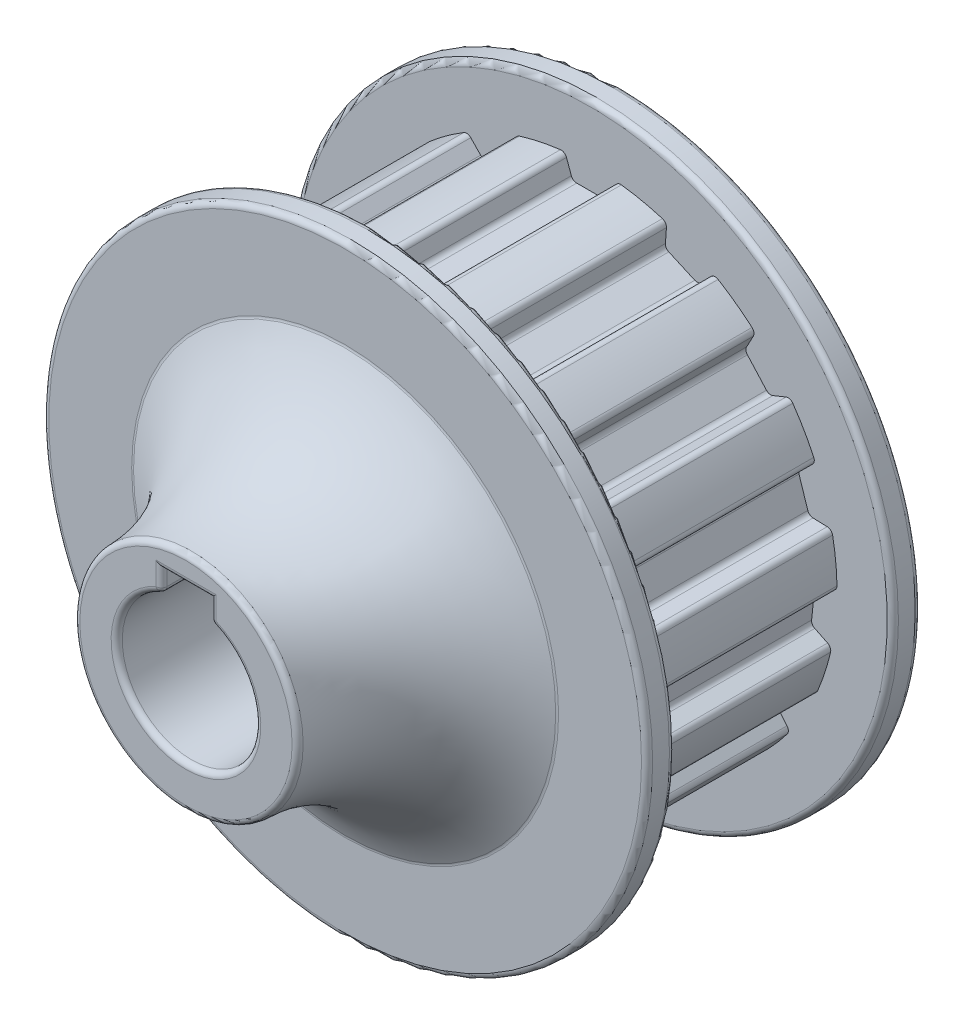
SolidWorks part; units mm, degrees
ref_plane "Front Plane" through (0, 0, 0) normal (0, 0, 1) x (1, 0, 0)
ref_plane "Top Plane" through (0, 0, 0) normal (0, 1, 0) x (1, 0, 0)
ref_plane "Right Plane" through (0, 0, 0) normal (1, 0, 0) x (0, 0, -1)
sketch "Sketch1" plane through (0, 0, 0) normal (0, 1, 0) x (1, 0, 0)
  line L0 (0, 36.1296) -> (0, -19.4741) construction
sketch "Sketch7" plane through (0, 0, 0) normal (0, 0, 1) x (1, 0, 0)
  line L0 (0, 0) -> (0, 20.9536) construction
  line L1 (-2.325, 21.9086) -> (-2.9401, 23.5986) construction
  line L2 (-2.325, 21.9086) -> (-1.6298, 19.9986) construction
  line L3 (-1.6298, 19.9986) -> (1.6298, 19.9986) construction
  line L4 (1.6298, 19.9986) -> (2.325, 21.9086) construction
  line L5 (2.325, 21.9086) -> (-2.325, 21.9086) construction
  line L6 (0, 19.9986) -> (0, 21.9086) construction
  line L7 (2.325, 21.9086) -> (2.9401, 23.5986) construction
  line L8 (-2.9401, 23.5986) -> (2.9401, 23.5986) construction
  line L9 (0, 0) -> (8.5226, 19.1421) construction
  line L10 (8.5226, 19.1421) -> (8.9611, 20.1269) construction
  line L11 (0, 21.9086) -> (0, 22.0316) construction
  line L12 (0, 22.0316) -> (0, 23.7811) construction
  line L13 (0, 22.9064) -> (9.3169, 20.926) construction
  line L14 (8.9611, 20.1269) -> (9.6726, 21.7251) construction
  circle A1 centre (0, 0) radius 20.9536 construction
  circle A2 centre (-1.2727, 20.5086) radius 0.51 construction
  circle A3 centre (1.2727, 20.5086) radius 0.51 construction
  circle A4 centre (0, 0) radius 22.0316
  circle A5 centre (0, 0) radius 23.7811 construction
  dimension "D3" = 40
  dimension "D6" = 1.02
  dimension "D1" = 3.6
  dimension "D2" = 24
  dimension "D7" = 9.525
  dimension "D4" = 1.91
  dimension "D5" = 4.65
extrude "Boss-Extrude1" add sketch "Sketch7" along normal blind 7.25 and the other way blind 7.25 contours A4 region at (0, 0, 0)
sketch "Sketch14" plane through (0, 0, 0) normal (1, 0, 0) x (0, 0, -1)
  line L0 (-21.5, 0) -> (-21.5, 10)
  line L1 (-21.5, 0) -> (0, 0)
  line L2 (0, 0) -> (0, 19)
  line L3 (0, 19) -> (-7.25, 19)
  line L4 (-7.25, 19) -> (-21.5, 10)
  line L5 (-7.25, 22.0316) -> (-7.25, -22.0316) construction
  line L6 (-21.5, 7.0431) -> (-2.5683, 19) construction
  arc A0 (-7.25, 19) -> (-21.5, 10) centre (-21.2919, 25.4517) cw
  dimension "D1" = 10
  dimension "D2" = 19
  dimension "D3" = 21.5
  dimension "D4" = 2.5
revolve "Revolve1" add sketch "Sketch14" angle 360 about L0 region at (0, 7.3866, 9.0486) region at (0, 9.3218, 19.3148) region at (0, 17.2024, 6.8722)
sketch "Sketch9" plane through (0, 0, 0) normal (0, 0, 1) x (1, 0, 0)
  line L0 (2, 0) -> (-2, 0) construction
  line L1 (-2, 0) -> (-2, 7.5) construction
  line L2 (-2, 7.5) -> (2, 7.5) construction
  line L3 (2, 7.5) -> (2, 0) construction
  circle A0 centre (0, 0) radius 6 construction
  dimension "D1" = 12
  dimension "D2" = 4
  dimension "D3" = 7.5
sketch "Sketch10" plane through (0, 0, 0) normal (0, 0, 1) x (1, 0, 0)
  line L0 (2, 0) -> (-2, 0) construction
  line L1 (-2.2, 7.7) -> (2.2, 7.7)
  line L2 (-2.2, 7.7) -> (-2.2, 0)
  line L3 (-2.2, 0) -> (2.2, 0)
  line L4 (2.2, 7.7) -> (2.2, 0)
  line L5 (-2, 7.5) -> (2, 7.5) construction
  line L6 (2, 7.5) -> (2, 0) construction
  circle A0 centre (0, 0) radius 6.2
  circle A1 centre (0, 0) radius 6 construction
  dimension "D1" = 0.2
  dimension "D2" = 0.2
  dimension "D3" = 0.2
extrude "Cut-Extrude3" cut sketch "Sketch10" against normal through all both and the other way through all contours A0 L4 L1 L2 | L2 A0 L4 L3 | L4 A0 L2 L3 region at (0, 6.8793, 0) region at (0, 3.0348, 0) region at (0, -0.8613, 0)
sketch "Sketch11" plane through (0, 0, 0) normal (0, 1, 0) x (1, 0, 0)
  line L0 (22.0316, 7.25) -> (-22.0316, 7.25) construction
  line L1 (11, 7.25) -> (17.5, 7.25)
  line L2 (11, 7.25) -> (11, 4.75)
  line L3 (11, 4.75) -> (17.5, 4.75)
  line L4 (17.5, 7.25) -> (17.5, 4.75)
  line L5 (-22.0316, -7.25) -> (22.0316, -7.25) construction
  line L6 (11, -7.25) -> (17.5, -7.25)
  line L7 (11, -7.25) -> (11, -4.75)
  line L8 (11, -4.75) -> (17.5, -4.75)
  line L9 (17.5, -7.25) -> (17.5, -4.75)
  line L11 (11, 4.75) -> (11, -4.75) construction
  line L12 (17.5, -4.75) -> (17.5, 4.75) construction
  line L13 (6.2, 7.25) -> (-6.2, 7.25) construction
  line L14 (0, 7.25) -> (22.5, 7.25)
  line L15 (0, 7.25) -> (0, -7.25)
  line L16 (0, -7.25) -> (22.5, -7.25)
  line L17 (22.5, 7.25) -> (22.5, -7.25)
  line L18 (-6.2, -7.25) -> (6.2, -7.25) construction
  line L19 (6, 7.25) -> (6, -7.25) construction
  dimension "D1" = 22.5
  dimension "D2" = 6
  dimension "D3" = 5
  dimension "D4" = 5
  dimension "D5" = 2.5
revolve "Cut-Revolve1" [suppressed] cut sketch "Sketch11" angle 360 about L0
sketch "Sketch15" plane through (0, 0, -7.25) normal (0, 0, -1) x (-1, 0, 0)
  circle A0 centre (0, 0) radius 8.0081
  circle A1 centre (0, 0) radius 2.25
  dimension "D1" = 4.5
extrude "Boss-Extrude2" add sketch "Sketch15" against normal blind 5.5
sketch "Sketch16" plane through (0, 0, -7.25) normal (0, 0, -1) x (-1, 0, 0)
  circle A0 centre (0, 0) radius 5
  dimension "D1" = 10
extrude "Cut-Extrude4" cut sketch "Sketch16" against normal blind 3
sketch "Sketch17" plane through (0, 0, -7.25) normal (0, 0, -1) x (-1, 0, 0)
  circle A0 centre (0, 0) radius 22.0316
  circle A1 centre (0, 0) radius 22.0316 construction
  circle A2 centre (0, 0) radius 5
  circle A3 centre (0, 0) radius 5 construction
extrude "Boss-Extrude3" add sketch "Sketch17" along normal blind 7.5
sketch "Sketch8" plane through (0, 0, 0) normal (0, 0, 1) x (1, 0, 0)
  line L6 (-1.6298, 19.9986) -> (-2.3698, 22.0316)
  line L7 (-2.3698, 22.0316) -> (2.3698, 22.0316)
  line L8 (2.3698, 22.0316) -> (1.6298, 19.9986)
  line L9 (1.6298, 19.9986) -> (-1.6298, 19.9986)
  line L10 (-2.325, 21.9086) -> (-1.6298, 19.9986) construction
  line L11 (1.6298, 19.9986) -> (2.325, 21.9086) construction
  line L12 (6.6453, 18.9326) -> (6.7962, 21.0908)
  line L13 (6.7962, 21.0908) -> (11.126, 19.163)
  line L14 (11.126, 19.163) -> (9.6231, 17.6067)
  line L15 (9.6231, 17.6067) -> (6.6453, 18.9326)
  line L16 (13.7713, 14.5929) -> (14.787, 16.5031)
  line L17 (14.787, 16.5031) -> (17.9584, 12.981)
  line L18 (17.9584, 12.981) -> (15.9524, 12.1705)
  line L19 (15.9524, 12.1705) -> (13.7713, 14.5929)
  line L20 (18.5162, 7.73) -> (20.221, 9.0619)
  line L21 (20.221, 9.0619) -> (21.6856, 4.5544)
  line L22 (21.6856, 4.5544) -> (19.5235, 4.6299)
  line L23 (19.5235, 4.6299) -> (18.5162, 7.73)
  line L24 (20.0594, -0.4695) -> (22.1587, 0.0539)
  line L25 (22.1587, 0.0539) -> (21.6632, -4.6597)
  line L26 (21.6632, -4.6597) -> (19.7187, -3.7113)
  line L27 (19.7187, -3.7113) -> (20.0594, -0.4695)
  line L28 (18.1342, -8.5879) -> (20.2649, -8.9635)
  line L29 (20.2649, -8.9635) -> (17.8951, -13.0681)
  line L30 (17.8951, -13.0681) -> (16.5044, -11.4108)
  line L31 (16.5044, -11.4108) -> (18.1342, -8.5879)
  line L32 (13.0734, -15.2212) -> (14.8671, -16.4311)
  line L33 (14.8671, -16.4311) -> (11.0327, -19.2169)
  line L34 (11.0327, -19.2169) -> (10.4363, -17.1372)
  line L35 (10.4363, -17.1372) -> (13.0734, -15.2212)
  line L36 (5.7521, -19.2227) -> (6.8986, -21.0575)
  line L37 (6.8986, -21.0575) -> (2.2626, -22.0429)
  line L38 (2.2626, -22.0429) -> (2.5637, -19.9005)
  line L39 (2.5637, -19.9005) -> (5.7521, -19.2227)
  line L40 (-2.5637, -19.9005) -> (-2.2626, -22.0429)
  line L41 (-2.2626, -22.0429) -> (-6.8986, -21.0575)
  line L42 (-6.8986, -21.0575) -> (-5.7521, -19.2227)
  line L43 (-5.7521, -19.2227) -> (-2.5637, -19.9005)
  line L44 (-10.4363, -17.1372) -> (-11.0327, -19.2169)
  line L45 (-11.0327, -19.2169) -> (-14.8671, -16.4311)
  line L46 (-14.8671, -16.4311) -> (-13.0734, -15.2212)
  line L47 (-13.0734, -15.2212) -> (-10.4363, -17.1372)
  line L48 (-16.5044, -11.4108) -> (-17.8951, -13.0681)
  line L49 (-17.8951, -13.0681) -> (-20.2649, -8.9635)
  line L50 (-20.2649, -8.9635) -> (-18.1342, -8.5879)
  line L51 (-18.1342, -8.5879) -> (-16.5044, -11.4108)
  line L52 (-19.7187, -3.7113) -> (-21.6632, -4.6597)
  line L53 (-21.6632, -4.6597) -> (-22.1587, 0.0539)
  line L54 (-22.1587, 0.0539) -> (-20.0594, -0.4695)
  line L55 (-20.0594, -0.4695) -> (-19.7187, -3.7113)
  line L56 (-19.5235, 4.6299) -> (-21.6856, 4.5544)
  line L57 (-21.6856, 4.5544) -> (-20.221, 9.0619)
  line L58 (-20.221, 9.0619) -> (-18.5162, 7.73)
  line L59 (-18.5162, 7.73) -> (-19.5235, 4.6299)
  line L60 (-15.9524, 12.1705) -> (-17.9584, 12.981)
  line L61 (-17.9584, 12.981) -> (-14.787, 16.5031)
  line L62 (-14.787, 16.5031) -> (-13.7713, 14.5929)
  line L63 (-13.7713, 14.5929) -> (-15.9524, 12.1705)
  line L64 (-9.6231, 17.6067) -> (-11.126, 19.163)
  line L65 (-11.126, 19.163) -> (-6.7962, 21.0908)
  line L66 (-6.7962, 21.0908) -> (-6.6453, 18.9326)
  line L67 (-6.6453, 18.9326) -> (-9.6231, 17.6067)
  circle A0 centre (0, 0) radius 22.0316 construction
  point P119 (0, 0)
  dimension "D1" = 15
extrude "Cut-Extrude2" cut sketch "Sketch8" against normal through all both and the other way through all
fillet "Fillet2" radius 0.51 60 edges at (-6.787, 20.9602, -3.75) (-11.035, 19.0689, -3.75) (-14.7256, 16.3875, -3.75) (-17.837, 12.9319, -3.75) (-20.1179, 8.9813, -3.75) (-21.5548, 4.5589, -3.75) (-22.0316, 0.0222, -3.75) (-21.5456, -4.6023, -3.75) (-20.1359, -8.9408, -3.75) (-17.8109, -12.9678, -3.75) (-14.7585, -16.3578, -3.75) (-10.9966, -19.0911, -3.75) (-6.8293, -20.9465, -3.75) (-2.2809, -21.9133, -3.75) (2.2809, -21.9133, -3.75) (6.8293, -20.9465, -3.75) (10.9966, -19.0911, -3.75) (14.7585, -16.3578, -3.75) (17.8109, -12.9678, -3.75) (20.1359, -8.9408, -3.75) (21.5456, -4.6023, -3.75) (22.0316, 0.0222, -3.75) (21.5548, 4.5589, -3.75) (20.1179, 8.9813, -3.75) (17.837, 12.9319, -3.75) (14.7256, 16.3875, -3.75) (11.035, 19.0689, -3.75) (6.787, 20.9602, -3.75) (2.325, 21.9086, -3.75) (-6.6453, 18.9326, -3.75) (-9.6231, 17.6067, -3.75) (-13.7713, 14.5929, -3.75) (-15.9524, 12.1705, -3.75) (-18.5162, 7.73, -3.75) (-19.5235, 4.6299, -3.75) (-20.0594, -0.4695, -3.75) (-19.7187, -3.7113, -3.75) (-18.1342, -8.5879, -3.75) (-16.5044, -11.4108, -3.75) (-13.0734, -15.2212, -3.75) (-10.4363, -17.1372, -3.75) (-5.7521, -19.2227, -3.75) (-2.5637, -19.9005, -3.75) (2.5637, -19.9005, -3.75) (5.7521, -19.2227, -3.75) (10.4363, -17.1372, -3.75) (13.0734, -15.2212, -3.75) (16.5044, -11.4108, -3.75) (18.1342, -8.5879, -3.75) (19.7187, -3.7113, -3.75) (20.0594, -0.4695, -3.75) (19.5235, 4.6299, -3.75) (18.5162, 7.73, -3.75) (15.9524, 12.1705, -3.75) (13.7713, 14.5929, -3.75) (9.6231, 17.6067, -3.75) (6.6453, 18.9326, -3.75) (1.6298, 19.9986, -3.75) (-1.6298, 19.9986, -3.75) (-2.325, 21.9086, -3.75)
sketch "Sketch18" plane through (0, 0, -14.75) normal (0, 0, -1) x (-1, 0, 0)
  circle A0 centre (0, 0) radius 5
  circle A1 centre (0, 0) radius 27.0316
  circle A2 centre (0, 0) radius 22.0316
  circle A3 centre (0, 0) radius 5 construction
  arc A4 (-2.7297, 21.8619) -> (-6.3983, 21.0821) centre (0, 0) ccw construction
  dimension "D1" = 5
extrude "Boss-Extrude4" add sketch "Sketch18" along normal blind 2.5 contours A1 A2 | A2 A0 region at (26.2671, 0, -14.75) region at (21.4085, 0, -14.75)
sketch "Sketch19" plane through (0, 0, 7.25) normal (0, 0, 1) x (1, 0, 0)
  circle A0 centre (0, 0) radius 19
  circle A1 centre (0, 0) radius 27.0316
  circle A2 centre (0, 0) radius 27.0316 construction
  circle A3 centre (0, 0) radius 19 construction
extrude "Boss-Extrude5" add sketch "Sketch19" against normal blind 2.5
fillet "Fillet3" radius 0.5 19 edges at (2.2, 5.7966, 9.875) (-2.2, 5.7966, 9.875) (2.2, 6.7483, 21.5) (-2.2, 6.7483, 21.5) (0, 7.7, 21.5) (-19, 0, 7.25) (-10, 0, 21.5) (0, -6.2, 21.5) (-5, 0, -4.25) (-2.25, 0, -4.25) (-2.2, 6.7483, -1.75) (2.2, 6.7483, -1.75) (27.0316, 0, 4.75) (-27.0316, 0, -14.75) (-27.0316, 0, -17.25) (27.0316, 0, 7.25) (0, 7.7, -1.75) (0, -6.2, -1.75) (-5, 0, -17.25)
